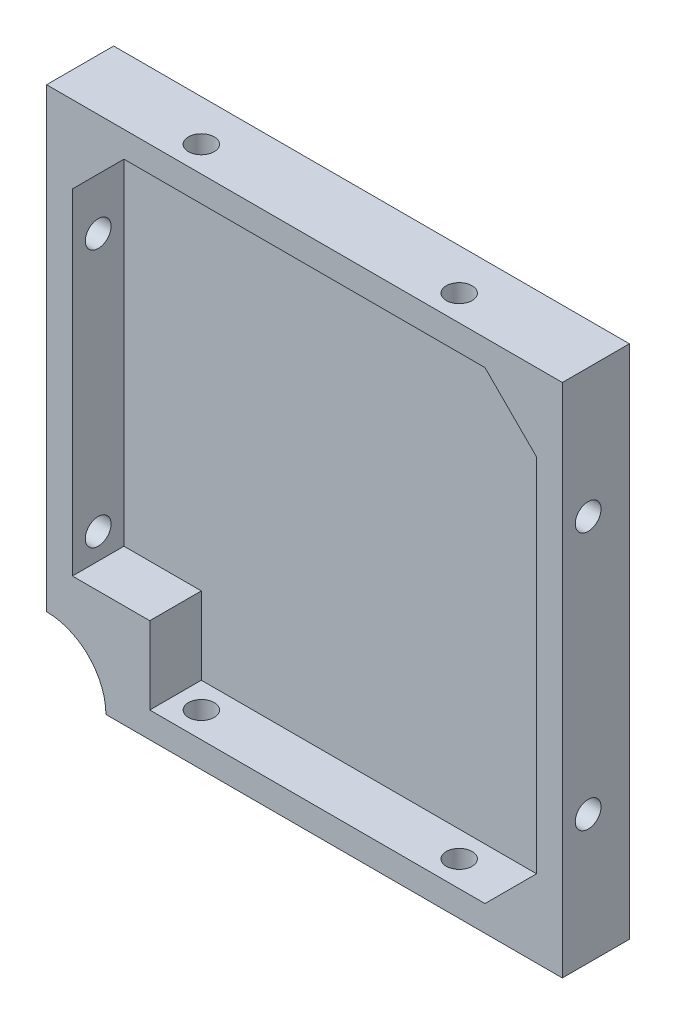
SolidWorks part; units mm, degrees
ref_plane "Plan de face" through (0, 0, 0) normal (0, 0, 1) x (1, 0, 0)
ref_plane "Plan de dessus" through (0, 0, 0) normal (0, 1, 0) x (1, 0, 0)
ref_plane "Plan de droite" through (0, 0, 0) normal (1, 0, 0) x (0, 0, -1)
sketch "Esquisse1" plane through (0, 0, 0) normal (0, 0, 1) x (1, 0, 0)
  line L0 (44.1184, 33.7284) -> (54.1184, 33.7284)
  line L1 (-45.8816, 33.7284) -> (44.1184, 33.7284)
  line L2 (-45.8816, 33.7284) -> (-45.8816, -66.2716)
  line L3 (-45.8816, -66.2716) -> (54.1184, -66.2716)
  line L4 (54.1184, 23.7284) -> (54.1184, -66.2716)
  line L5 (54.1184, 33.7284) -> (54.1184, 23.7284)
  point P6 (54.1184, 33.7284)
  dimension "D1" = 100
  dimension "D2" = 100
extrude "Boss.-Extru.1" add sketch "Esquisse1" along normal blind 13
shell "Coque1" thickness 5 removed face at (4.1184, -16.2716, 13)
sketch "Esquisse2" plane through (-45.8816, 0, 0) normal (-1, 0, 0) x (0, 0, 1)
  line L0 (13, 33.7284) -> (13, -66.2716) construction
  line L1 (13, 33.7284) -> (0, 33.7284) construction
  line L2 (13, -66.2716) -> (0, -66.2716) construction
  circle A0 centre (8, 8.7284) radius 2.5
  circle A1 centre (8, -41.2716) radius 2.5
  dimension "D1" = 5
  dimension "D2" = 5
  dimension "D3" = 5
  dimension "D4" = 5
  dimension "D5" = 25
  dimension "D6" = 25
extrude "Enlèv. mat.-Extru.1" cut sketch "Esquisse2" against normal up to surface (100 mm away) contours A1 | A0 region at (-45.8816, -41.2716, 8) up to face at (54.1184, -16.2716, 6.5)
sketch "Esquisse3" plane through (0, -66.2716, 0) normal (0, -1, 0) x (1, 0, 0)
  line L0 (-45.8816, 13) -> (54.1184, 13) construction
  line L2 (54.1184, 13) -> (54.1184, 0) construction
  line L3 (-45.8816, 13) -> (-45.8816, 0) construction
  circle A0 centre (-20.8816, 8) radius 2.5
  circle A1 centre (29.1184, 8) radius 2.5
  dimension "D1" = 5
  dimension "D2" = 5
  dimension "D3" = 5
  dimension "D4" = 5
  dimension "D5" = 25
  dimension "D6" = 25
extrude "Enlèv. mat.-Extru.2" cut sketch "Esquisse3" against normal up to surface (100 mm away) up to face at (4.1184, 33.7284, 6.5)
sketch "Esquisse4" plane through (0, 0, 3) normal (0, 0, 1) x (1, 0, 0)
  line L0 (-30.8816, 28.7284) -> (-40.8816, 18.7284)
  line L1 (49.1184, 28.7284) -> (-40.8816, 28.7284) construction
  line L2 (-40.8816, 28.7284) -> (-40.8816, -61.2716) construction
  line L3 (-40.8816, 18.7284) -> (-40.8816, 28.7284)
  line L4 (-40.8816, 28.7284) -> (-30.8816, 28.7284)
  line L5 (49.1184, 28.7284) -> (49.1184, 18.7284)
  line L6 (49.1184, -61.2716) -> (49.1184, 28.7284) construction
  line L7 (49.1184, 18.7284) -> (39.1184, 28.7284)
  line L8 (39.1184, 28.7284) -> (49.1184, 28.7284)
  line L9 (49.1184, 28.7284) -> (-40.8816, 28.7284) construction
  line L10 (49.1184, -61.2716) -> (49.1184, -51.2716)
  line L11 (49.1184, -51.2716) -> (39.1184, -61.2716)
  line L12 (-40.8816, -61.2716) -> (49.1184, -61.2716) construction
  line L13 (39.1184, -61.2716) -> (49.1184, -61.2716)
  line L14 (-40.8816, -46.2716) -> (-25.8816, -46.2716)
  line L16 (-25.8816, -46.2716) -> (-25.8816, -61.2716)
  line L17 (-25.8816, -61.2716) -> (-40.8816, -61.2716)
  line L18 (-40.8816, -61.2716) -> (-40.8816, -46.2716)
  dimension "D1" = 10
  dimension "D2" = 10
  dimension "D3" = 10
  dimension "D4" = 10
  dimension "D5" = 10
  dimension "D6" = 10
  dimension "D7" = 15
  dimension "D8" = 15
extrude "Boss.-Extru.2" add sketch "Esquisse4" along normal up to surface (10 mm away) up to face at (4.1184, -16.2716, 13)
sketch "Esquisse5" plane through (0, 0, 13) normal (0, 0, 1) x (1, 0, 0)
  circle A0 centre (-45.8816, -66.2716) radius 11.5
  dimension "D1" = 23
extrude "Enlèv. mat.-Extru.3" cut sketch "Esquisse5" against normal up to surface (13 mm away) up to face at (4.1184, -16.2716, 0)
